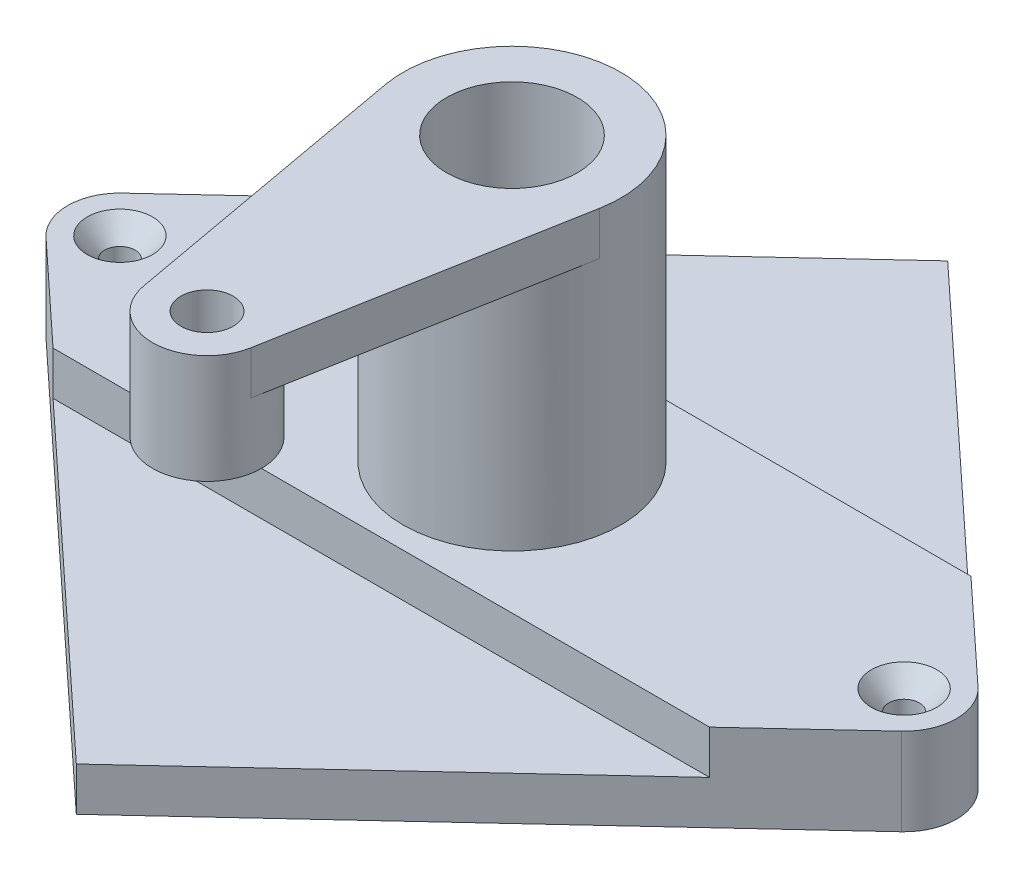
SolidWorks part; units mm, degrees
ref_plane "Alzado" through (0, 0, 0) normal (0, 0, 1) x (1, 0, 0)
ref_plane "Planta" through (0, 0, 0) normal (0, 1, 0) x (1, 0, 0)
ref_plane "Vista lateral" through (0, 0, 0) normal (1, 0, 0) x (0, 0, -1)
sketch "Sketch2" plane through (0, 0, 0) normal (0, 1, 0) x (1, 0, 0)
  line L0 (-753.4091, -300) -> (0, -1000)
  line L1 (-753.4091, -300) -> (753.4091, -300)
  line L2 (-753.4091, -300) -> (-753.4091, 300) construction
  line L3 (-753.4091, 300) -> (753.4091, 300)
  line L4 (753.4091, -300) -> (753.4091, 300) construction
  line L5 (-753.4091, -300) -> (753.4091, 300) construction
  line L6 (-753.4091, 300) -> (753.4091, -300) construction
  line L7 (0, -1000) -> (753.4091, -300)
  line L8 (753.4091, 300) -> (0, 1000)
  line L9 (0, 1000) -> (-753.4091, 300)
  line L10 (753.4091, 300) -> (981.6796, 87.9116)
  line L11 (753.4091, -300) -> (981.6796, -87.9116)
  line L14 (-981.6796, -87.9116) -> (-753.4091, -300)
  line L15 (-981.6796, 87.9116) -> (-753.4091, 300)
  circle A0 centre (0, 0) radius 250
  arc A1 (981.6796, -87.9116) -> (981.6796, 87.9116) centre (900, 0) ccw
  arc A2 (-981.6796, 87.9116) -> (-981.6796, -87.9116) centre (-900, 0) ccw
  dimension "D2" = 500
  dimension "D7" = 240
  dimension "D8" = 240
  dimension "D1" = 600
  dimension "D3" = 1000
  dimension "D4" = 1000
  dimension "D5" = 900
  dimension "D6" = 900
extrude "Boss-Extrude1" add sketch "Sketch2" along normal blind 650 and the other way blind 200 contours A0 region at (0, 0, 0)
extrude "Boss-Extrude2" add sketch "Sketch2<3>" against normal blind 200 contours L15 A2 L14 L1 L11 A1 L10 L3 A0 | A1 L10 L8 L9 L15 A2 L14 L0 L7 L11 region at (-853.0707, 0, 178.3778)
sketch "Sketch2<3>" plane through (0, 0, 0) normal (0, 1, 0) x (1, 0, 0) same geometry as "Sketch2"
extrude "Cut-Extrude1" cut sketch "Sketch2<5>" against normal blind 100 contours L0 L7 L1 | L8 L9 L3 region at (0, 0, 533.3333) region at (0, 0, -533.3333)
sketch "Sketch2<5>" plane through (0, 0, 0) normal (0, 1, 0) x (1, 0, 0) same geometry as "Sketch2"
sketch "Sketch3" plane through (0, 650, 0) normal (0, 1, 0) x (1, 0, 0)
  line L0 (-245.9817, -44.6429) -> (-122.9909, -722.3214)
  line L1 (245.9817, -44.6429) -> (122.9909, -722.3214)
  circle A0 centre (0, -700) radius 125
  arc A1 (245.9817, -44.6429) -> (-245.9817, -44.6429) centre (0, 0) ccw construction
  circle A2 centre (0, 0) radius 250 construction
  circle M4 centre (0, 0) radius 250
  dimension "D2" = 250
  dimension "D1" = 700
extrude "Boss-Extrude4" add sketch "Sketch3" against normal blind 100 contours A0 L1 L0 M4 region at (0, 650, 393.9889)
extrude "Boss-Extrude5" add sketch "Sketch3<3>" against normal blind 250 contours A0 region at (0, 650, 700)
sketch "Sketch3<3>" plane through (0, 650, 0) normal (0, 1, 0) x (1, 0, 0) same geometry as "Sketch3"
hole_wizard "CSK for #0 Flat Head Machine Screw1" positions "Sketch6" profile "Sketch7" countersink size "#0" standard "ANSI Inch" end condition through all
sketch "Sketch6" plane through (0, 0, 0) normal (0, 1, 0) x (1, 0, 0)
  point P0 (900, 0)
  point P2 (-900, 0)
  dimension "D1" = 900
  dimension "D2" = 900
sketch "Sketch7" plane through (900, 0, 0) normal (1, 0, 0) x (0, 0, 1)
  line L0 (0, 0) -> (0, 200)
  line L1 (0, 200) -> (35, 200)
  line L2 (35, 200) -> (35, 46.0147)
  line L3 (35, 46.0147) -> (75, 0)
  line L5 (75, 0) -> (0, 0)
  line L6 (-35, 46.0147) -> (-75, 0) construction
  line L11 (0, -6.35) -> (0, 107.95) construction
  dimension "Thru Hole Dia." = 70
  dimension "Thru Hole Depth" = 200
  dimension "Near C'Sink Dia." = 150
  dimension "Near C'Sink Angle" = 82
hole_wizard "CBORE for #0 Binding Head Machine Screw1" positions "Sketch8" profile "Sketch10" counterbore size "#0" standard "ANSI Inch"
sketch "Sketch8" plane through (0, 650, 0) normal (0, 1, 0) x (1, 0, 0)
  point P0 (0, 0)
sketch "Sketch10" plane through (0, 650, 0) normal (1, 0, 0) x (0, 0, 1)
  line L0 (0, 0) -> (0, 450)
  line L1 (0, 450) -> (40, 425.9656)
  line L2 (40, 425.9656) -> (40, 350)
  line L3 (40, 350) -> (150, 350)
  line L4 (150, 350) -> (150, 0)
  line L5 (150, 0) -> (0, 0)
  line L10 (0, 450) -> (-40, 425.9656) construction
  line L11 (0, -6.35) -> (0, 107.95) construction
  dimension "Hole Dia." = 80
  dimension "Hole Depth" = 450
  dimension "C'Bore Dia." = 300
  dimension "C'Bore Depth" = 350
  dimension "Drill Angle" = 118
hole_wizard "Hole1" positions "Sketch11" profile "Sketch13" legacy end condition up to next
sketch "Sketch11" plane through (0, 650, 0) normal (0, 1, 0) x (1, 0, 0)
  point P0 (0, -700)
  point P4 (0, 0)
  dimension "D1" = 700
sketch "Sketch13" plane through (0, 650, 700) normal (1, 0, 0) x (0, 0, 1)
  line L0 (0, 0) -> (0, 250)
  line L1 (0, 250) -> (60, 250)
  line L2 (60, 250) -> (60, 0)
  line L3 (60, 0) -> (0, 0)
  line L4 (0, 110) -> (0, -10) construction
  dimension "Diameter" = 120
  dimension "Depth" = 250
